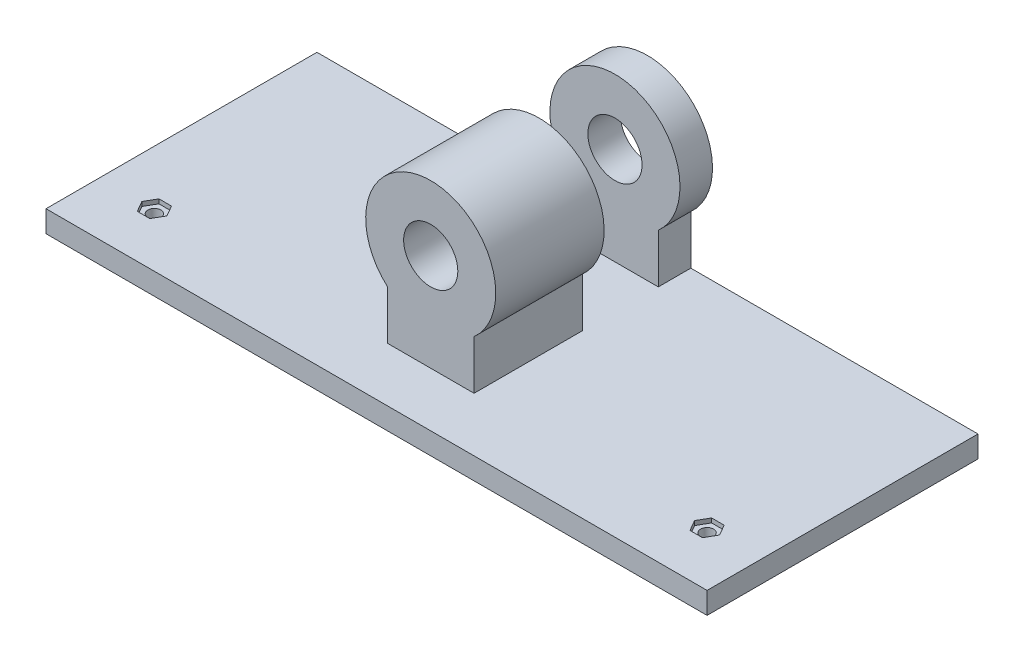
SolidWorks part; units mm, degrees
ref_plane "Front Plane" through (0, 0, 0) normal (0, 0, 1) x (1, 0, 0)
ref_plane "Top Plane" through (0, 0, 0) normal (0, 1, 0) x (1, 0, 0)
ref_plane "Right Plane" through (0, 0, 0) normal (1, 0, 0) x (0, 0, -1)
sketch "Sketch1" plane through (0, 0, 0) normal (0, 1, 0) x (1, 0, 0)
  line L0 (152.5, 125) -> (152.5, 0) construction
  line L1 (0, 0) -> (305, 0)
  line L2 (0, 0) -> (0, 125)
  line L3 (0, 125) -> (305, 125)
  line L4 (305, 0) -> (305, 125)
  line L5 (25, 100) -> (280, 100) construction
  line L6 (280, 25) -> (280, 100) construction
  line L7 (25, 25) -> (280, 25) construction
  line L8 (25, 25) -> (25, 100) construction
  line L9 (152.5, 62.5) -> (25, 62.5) construction
  line L10 (30.7735, 100) -> (27.8868, 105) construction
  line L11 (27.8868, 105) -> (22.1132, 105) construction
  line L12 (22.1132, 105) -> (19.2265, 100) construction
  line L13 (19.2265, 100) -> (22.1132, 95) construction
  line L14 (22.1132, 95) -> (27.8868, 95) construction
  line L15 (27.8868, 95) -> (30.7735, 100) construction
  line L16 (27.8868, 30) -> (30.7735, 25) construction
  line L17 (22.1132, 30) -> (27.8868, 30) construction
  line L18 (19.2265, 25) -> (22.1132, 30) construction
  line L19 (22.1132, 20) -> (19.2265, 25) construction
  line L20 (27.8868, 20) -> (22.1132, 20) construction
  line L21 (30.7735, 25) -> (27.8868, 20) construction
  line L22 (282.8868, 30) -> (277.1132, 30) construction
  line L23 (285.7735, 25) -> (282.8868, 30) construction
  line L24 (282.8868, 20) -> (285.7735, 25) construction
  line L25 (277.1132, 20) -> (282.8868, 20) construction
  line L26 (274.2265, 25) -> (277.1132, 20) construction
  line L27 (277.1132, 30) -> (274.2265, 25) construction
  line L28 (277.1132, 95) -> (274.2265, 100) construction
  line L29 (282.8868, 95) -> (277.1132, 95) construction
  line L30 (285.7735, 100) -> (282.8868, 95) construction
  line L31 (282.8868, 105) -> (285.7735, 100) construction
  line L32 (277.1132, 105) -> (282.8868, 105) construction
  line L33 (274.2265, 100) -> (277.1132, 105) construction
  circle A1 centre (25, 100) radius 5 construction
  circle A3 centre (280, 25) radius 3
  circle A4 centre (25, 25) radius 3
  dimension "D3" = 6
  dimension "D1" = 305
  dimension "D2" = 125
  dimension "D5" = 10
  dimension "D4" = 25
extrude "Boss-Extrude1" add sketch "Sketch1" along normal blind 10
sketch "Sketch6" plane through (0, 10, 0) normal (0, 1, 0) x (1, 0, 0)
  line L0 (152.5, 125) -> (152.5, 0) construction
  line L7 (305, 125) -> (0, 125) construction
  line L8 (0, 0) -> (305, 0) construction
  line L9 (152.5, 62.5) -> (0, 62.5) construction
  line L10 (0, 125) -> (0, 0) construction
  line L29 (27.8868, 30) -> (30.7735, 25)
  line L30 (274.2265, 25) -> (277.1132, 20)
  line L31 (277.1132, 20) -> (282.8868, 20)
  line L32 (282.8868, 20) -> (285.7735, 25)
  line L33 (285.7735, 25) -> (282.8868, 30)
  line L34 (282.8868, 30) -> (277.1132, 30)
  line L35 (277.1132, 30) -> (274.2265, 25)
  line L36 (22.1132, 30) -> (27.8868, 30)
  line L37 (19.2265, 25) -> (22.1132, 30)
  line L38 (22.1132, 20) -> (19.2265, 25)
  line L39 (27.8868, 20) -> (22.1132, 20)
  line L40 (30.7735, 25) -> (27.8868, 20)
  circle A0 centre (280, 25) radius 5 construction
  dimension "D1" = 10
extrude "Cut-Extrude1" cut sketch "Sketch6" against normal blind 2
sketch "Sketch7" plane through (0, 10, 0) normal (0, 1, 0) x (1, 0, 0)
  line L0 (0, 0) -> (305, 0) construction
  line L1 (132.5, 25) -> (172.5, 25)
  line L2 (132.5, 25) -> (132.5, 75)
  line L3 (132.5, 75) -> (172.5, 75)
  line L4 (172.5, 25) -> (172.5, 75)
  line L5 (152.5, 0) -> (152.5, 125) construction
  line L6 (305, 125) -> (0, 125) construction
  line L7 (172.5, 75) -> (172.5, 125) construction
  line L18 (132.5, 110) -> (172.5, 110)
  line L19 (132.5, 110) -> (132.5, 125)
  line L20 (132.5, 125) -> (172.5, 125)
  line L21 (172.5, 110) -> (172.5, 125)
  point P11 (152.5, 75)
  point P20 (152.5, 110)
  dimension "D1" = 40
  dimension "D2" = 50
  dimension "D4" = 15
extrude "Boss-Extrude2" add sketch "Sketch7" along normal blind 22.6393
sketch "Sketch11" plane through (0, 0, -25) normal (0, 0, 1) x (1, 0, 0)
  circle A0 centre (152.5, 55) radius 30
  circle A1 centre (152.5, 55) radius 12.5
  dimension "D1" = 60
  dimension "D2" = 25
extrude "Boss-Extrude3" add sketch "Sketch11" against normal up to surface (100 mm away) up to face at (152.5, 13.1598, -125)
ref_plane "Plane1" through (0, 0, -62.5) normal (0, 0, 1) x (1, 0, 0)
sketch "Sketch12" plane through (305, 0, 0) normal (1, 0, 0) x (0, 0, -1)
  line L0 (125, 85) -> (25, 85) construction
  line L1 (75, 10) -> (110, 10)
  line L2 (75, 10) -> (75, 85)
  line L3 (75, 85) -> (110, 85)
  line L4 (110, 10) -> (110, 85)
  line L6 (110, 32.6393) -> (110, 10) construction
extrude "Cut-Extrude2" cut sketch "Sketch12" against normal through all
equation "\"joint_width\"=4"
equation "\"D2@Sketch7\"=5"
equation "\"short_base_length\"=12.5"
equation "\"D2@Sketch1\"=\"short_base_length\""
equation "\"outer_diam_main_joint\"=6"
equation "\"D1@Sketch11\"=\"outer_diam_main_joint\""
equation "\"D1@Sketch7\"=\"outer_diam_main_joint\"-2"
equation "\"D1@Boss-Extrude2\"=(\"outer_diam_main_joint\"/2)+1.5cm-sqr((\"outer_diam_main_joint\"/2)^2-((\"outer_diam_main_joint\"-2)/2)^2)"
